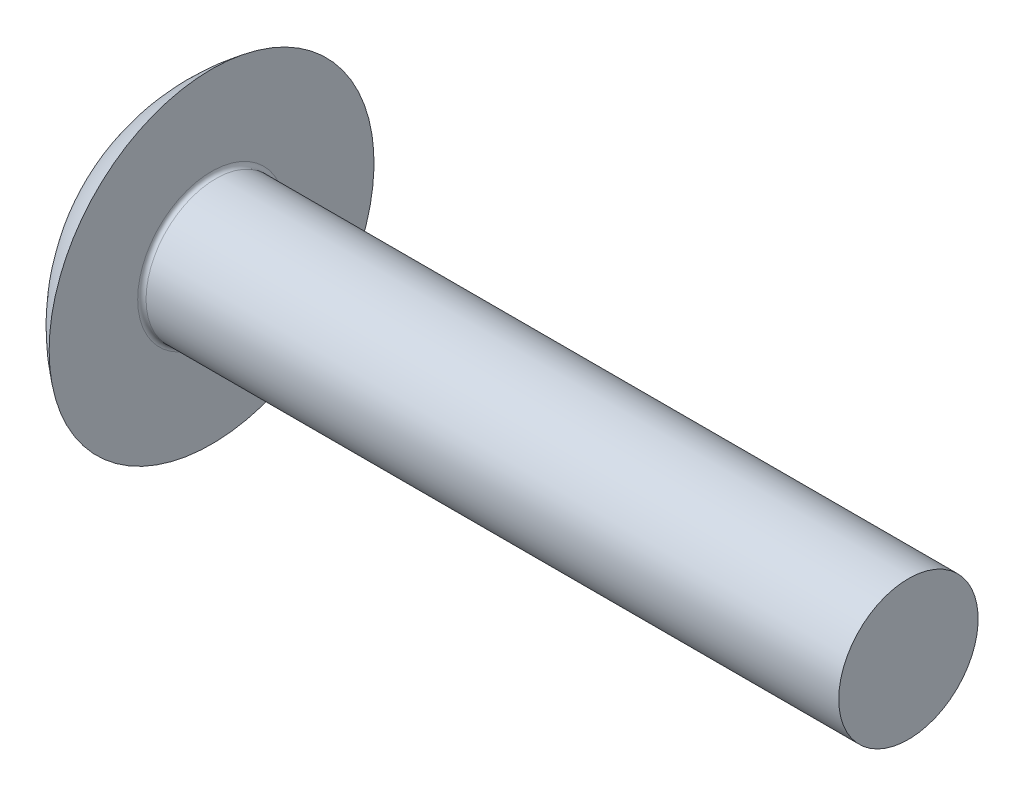
SolidWorks part; units mm, degrees
ref_plane "Front" through (0, 0, 0) normal (0, 0, 1) x (1, 0, 0)
ref_plane "Top" through (0, 0, 0) normal (0, 1, 0) x (1, 0, 0)
ref_plane "Right" through (0, 0, 0) normal (1, 0, 0) x (0, 0, -1)
sketch "Sketch1" plane through (0, 0, 0) normal (0, 0, 1) x (1, 0, 0)
  line L0 (-81.1665, 0) -> (18.3405, 0) construction
  line L1 (55.8733, 0) -> (55.8733, 5)
  line L2 (55.8733, 5) -> (5.8733, 5)
  line L3 (5.8733, 5) -> (5.8733, 11.6547)
  line L4 (55.8733, 0) -> (0, 0)
  arc A0 (5.8733, 11.6547) -> (0, 0) centre (14.5, 0) ccw
  dimension "R" = 14.5
  dimension "d" = 10
  dimension "l" = 50
  dimension "K" = 5.8733
revolve "Base-Revolve" add sketch "Sketch1" angle 360 about L0
fillet "Fillet1" radius 0.3 1 edges at (5.8733, 0, 5)
